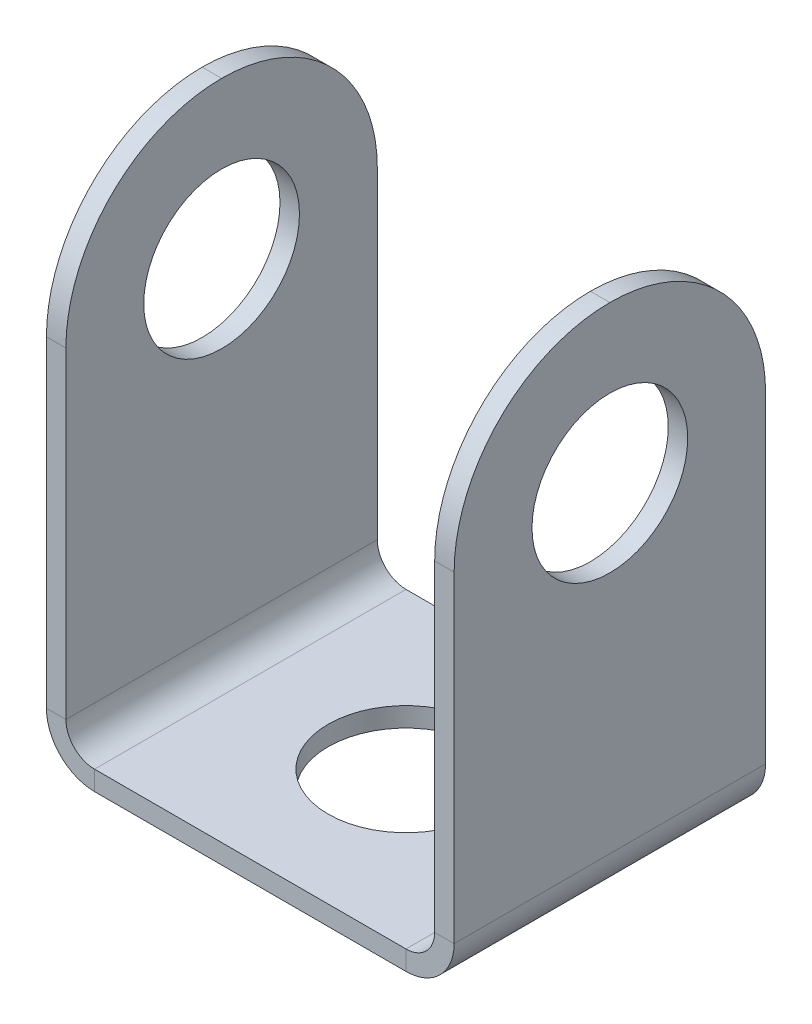
SolidWorks part; units mm, degrees
note: The reader was unsure of these and kept them because the rebuilt part matched: flange length of "Edge-Flange1", "Edge-Flange2".
ref_plane "Front Plane" through (0, 0, 0) normal (0, 0, 1) x (1, 0, 0)
ref_plane "Top Plane" through (0, 0, 0) normal (0, 1, 0) x (1, 0, 0)
ref_plane "Right Plane" through (0, 0, 0) normal (1, 0, 0) x (0, 0, -1)
sketch "Sketch1" plane through (0, 0, 0) normal (0, 1, 0) x (1, 0, 0)
  line L1 (-4, 4) -> (4, 4)
  line L2 (-4, 4) -> (-4, -4)
  line L3 (-4, -4) -> (4, -4)
  line L4 (4, 4) -> (4, -4)
  line L5 (-4, 4) -> (4, -4) construction
  line L6 (-4, -4) -> (4, 4) construction
  point P0 (0, 0)
base flange "Base-Flange1" sketch "Sketch1" thickness 0.5 reverse thickness direction yes parameters "D1"=0.7366
edge flange "Edge-Flange1" sketch "Sketch8" flange angle 90 flange length 13 flange position bend outside bend radius 0.7366 thickness 0.5 relief rectangular parameters "D6"=10
sketch "Sketch8" plane through (4, 0.5, 0) normal (1, 0, 0) x (0, 0, -1)
  line L0 (-4, 0) -> (4, 0) construction
  line L1 (-4, 0) -> (4, 0)
  line L2 (-4, 0) -> (-4, 13)
  line L3 (-4, 13) -> (4, 13)
  line L4 (4, 13) -> (4, 0)
bend "EdgeBend1" bend radius 0.7366 bend angle 90 parameters "D5"=1
edge flange "Edge-Flange2" sketch "Sketch11" flange angle 90 flange length 13 flange position bend outside bend radius 0.7366 thickness 0.5 relief rectangular parameters "D6"=10
sketch "Sketch11" plane through (-4, 0.5, 0) normal (-1, 0, 0) x (0, 0, 1)
  line L0 (-4, 0) -> (4, 0) construction
  line L1 (-4, 0) -> (4, 0)
  line L2 (-4, 0) -> (-4, 13)
  line L3 (-4, 13) -> (4, 13)
  line L4 (4, 13) -> (4, 0)
bend "EdgeBend2" bend radius 0.7366 bend angle 90 parameters "D5"=2
fillet "Fillet1" radius 4 4 edges at (4.9866, 13.5, -4) (-4.9866, 13.5, -4) (4.9866, 13.5, 4) (-4.9866, 13.5, 4)
sketch "Sketch12" plane through (0, 0.5, 0) normal (0, 1, 0) x (1, 0, 0)
  circle A0 centre (0, 0) radius 2
extrude "Cut-Extrude1" cut sketch "Sketch12" against normal through all normal cut yes
sketch "Sketch13" plane through (5.2366, 0, 0) normal (1, 0, 0) x (0, 0, -1)
  circle A0 centre (0, 9.4844) radius 2
extrude "Cut-Extrude2" cut sketch "Sketch13" against normal through all normal cut yes
sketch "Bend-Lines1" plane through (0, 0, 0) normal (0, 1, 0) x (1, 0, 0)
sketch "Bounding-Box1" plane through (0, 0, 0) normal (0, 1, 0) x (1, 0, 0)
sheet metal parameters "Sheet-Metal1" thickness 0.5 parameters "D1"=0.7366
flat pattern "Flat-Pattern1" [suppressed]
sketch "Bend-Lines2" plane through (0, 0, 0) normal (0, 1, 0) x (1, 0, 0)
sketch "Bounding-Box2" [suppressed] plane through (0, 0, 0) normal (0, 1, 0) x (1, 0, 0)
sheet metal parameters "Sheet-Metal2" thickness 0.5 parameters "D1"=0.7366
flat pattern "Flat-Pattern1" [suppressed]
sketch "Bend-Lines2" plane through (0, 0, 0) normal (0, 1, 0) x (1, 0, 0)
sketch "Bounding-Box2" [suppressed] plane through (0, 0, 0) normal (0, 1, 0) x (1, 0, 0)
bend of the flat pattern "Flatten-<EdgeBend1>1"
sheet metal parameters "Sheet-Metal3" thickness 0.5 parameters "D1"=0.7366
flat pattern "Flat-Pattern1" [suppressed]
sketch "Bend-Lines2" plane through (0, 0, 0) normal (0, 1, 0) x (1, 0, 0)
sketch "Bounding-Box2" [suppressed] plane through (0, 0, 0) normal (0, 1, 0) x (1, 0, 0)
bend of the flat pattern "Flatten-<EdgeBend1>1"
bend of the flat pattern "Flatten-<EdgeBend2>1"
sheet metal parameters "Sheet-Metal4" thickness 0.5 parameters "D1"=0.7366
flat pattern "Flat-Pattern1" [suppressed]
sketch "Bend-Lines2" plane through (0, 0, 0) normal (0, 1, 0) x (1, 0, 0)
sketch "Bounding-Box2" [suppressed] plane through (0, 0, 0) normal (0, 1, 0) x (1, 0, 0)
bend of the flat pattern "Flatten-<EdgeBend1>1"
bend of the flat pattern "Flatten-<EdgeBend2>1"
sheet metal parameters "Sheet-Metal5" thickness 0.5 parameters "D1"=0.7366
flat pattern "Flat-Pattern1" [suppressed]
sketch "Bend-Lines2" plane through (0, 0, 0) normal (0, 1, 0) x (1, 0, 0)
sketch "Bounding-Box2" [suppressed] plane through (0, 0, 0) normal (0, 1, 0) x (1, 0, 0)
bend of the flat pattern "Flatten-<EdgeBend1>1"
bend of the flat pattern "Flatten-<EdgeBend2>1"
